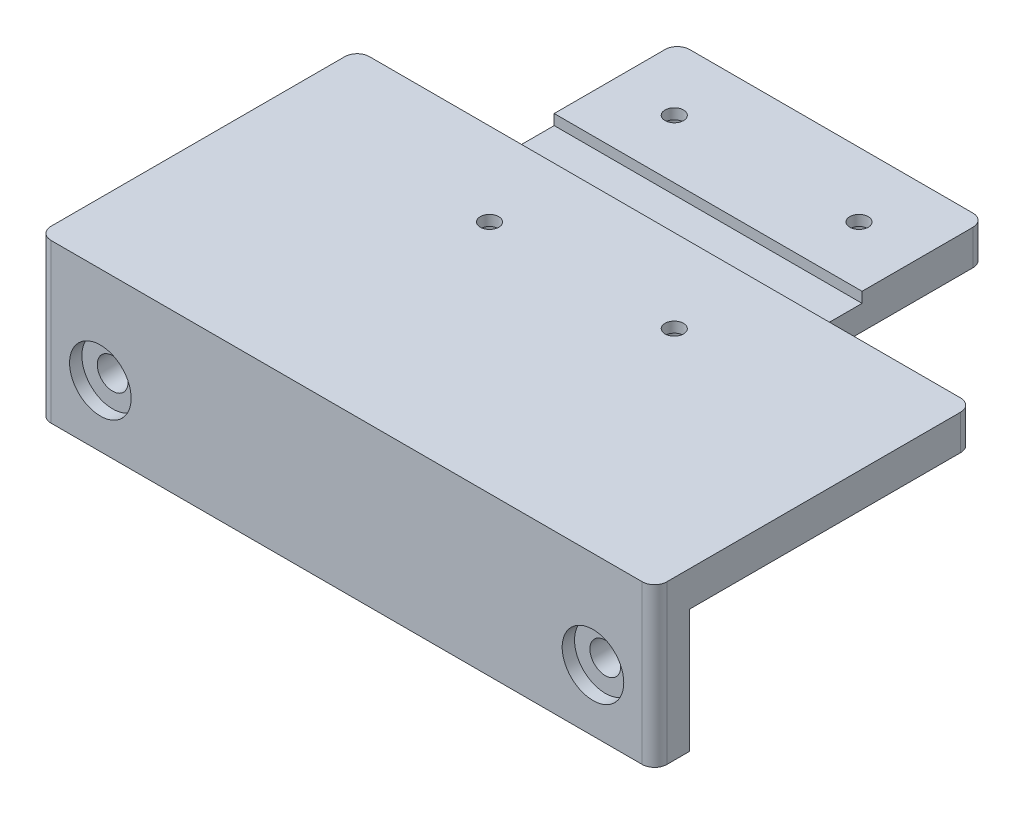
SolidWorks part; units mm, degrees
ref_plane "Front Plane" through (0, 0, 0) normal (0, 0, 1) x (1, 0, 0)
ref_plane "Top Plane" through (0, 0, 0) normal (0, 1, 0) x (1, 0, 0)
ref_plane "Right Plane" through (0, 0, 0) normal (1, 0, 0) x (0, 0, -1)
sketch "Sketch1" plane through (0, 0, 0) normal (1, 0, 0) x (0, 0, -1)
  line L0 (-20.5, 0) -> (-20.5, 5.5)
  line L1 (-20.5, 14.5) -> (-19.5, 14.5)
  line L2 (-19.5, 14.5) -> (-19.5, 5.5)
  line L3 (-19.5, 5.5) -> (-20.5, 5.5)
  line L4 (-20.5, 20) -> (-14.5, 20)
  line L5 (-20.5, 14.5) -> (-20.5, 20)
  line L6 (5.5, 20) -> (5.5, 19)
  line L7 (5.5, 19) -> (14.5, 19)
  line L8 (14.5, 19) -> (14.5, 20)
  line L9 (14.5, 20) -> (25.5, 20)
  line L10 (-5.5, 20) -> (-5.5, 19)
  line L11 (-5.5, 19) -> (-14.5, 19)
  line L12 (-14.5, 19) -> (-14.5, 20)
  line L13 (-5.5, 20) -> (5.5, 20)
  line L14 (-20.5, 0) -> (-26.2, 0)
  line L15 (-26.2, 0) -> (-26.2, 25.7)
  line L16 (-26.2, 25.7) -> (25.5, 25.7)
  line L17 (25.5, 25.7) -> (25.5, 20)
  line L19 (25.5, 24) -> (32.5, 24)
  line L20 (32.5, 24) -> (32.5, 25.7)
  line L21 (32.5, 25.7) -> (52.5, 25.7)
  line L22 (52.5, 25.7) -> (52.5, 20)
  line L23 (52.5, 20) -> (25.5, 20)
  point P8 (0, 20)
  point P22 (32.5, 28.1583)
  point P25 (25.1505, 20)
  point P28 (32.5, 23.1319)
  dimension "D1" = 20
  dimension "D2" = 9
  dimension "D3" = 1
  dimension "D4" = 46
  dimension "D5" = 11
  dimension "D6" = 5.7
  dimension "D7" = 11
  dimension "D8" = 7
  dimension "D9" = 20
  dimension "D10" = 4
extrude "Boss-Extrude1" add sketch "Sketch1" along normal mid plane 100 contours L17 L16 L15 L14 L0 L3 L2 L1 L5 L4 L12 L11 L10 L13 L6 L7 L8 L9 region at (0, 19.0839, 6.7595)
extrude "Boss-Extrude2" add sketch "Sketch1<3>" along normal mid plane 50 contours L23 L22 L21 L20 L19 L17 region at (0, 22.6824, -39.838)
sketch "Sketch1<3>" plane through (0, 0, 0) normal (1, 0, 0) x (0, 0, -1) same geometry as "Sketch1"
chamfer "Chamfer1" distance 1 12 edges at (0, 5.5, 19.5) (0, 14.5, 19.5) (0, 19, 14.5) (0, 19, 5.5) (0, 19, -5.5) (0, 19, -14.5) (-50, 10, 19.5) (50, 10, 19.5) (50, 19, 10) (-50, 19, 10) (50, 19, -10) (-50, 19, -10)
sketch "Sketch2" plane through (0, 20, 0) normal (0, -1, 0) x (1, 0, 0)
  line L0 (-25, -25.5) -> (-50, -25.5) construction
  line L2 (0, -52.5) -> (0, 26.2) construction
  line L3 (25, -52.5) -> (-25, -52.5) construction
  line L4 (50, 26.2) -> (-50, 26.2) construction
  line L5 (-25, -27) -> (25, -27) construction
  line L7 (-25, -52.5) -> (-25, -25.5) construction
  line L8 (25, -52.5) -> (25, -25.5) construction
  line L11 (-50, 5.5) -> (-50, -5.5) construction
  circle A0 centre (-15, -12) radius 1.5
  circle A1 centre (-15, -12) radius 2.5
  circle A2 centre (-15, -42) radius 2.5
  circle A3 centre (-15, -42) radius 1.5
  circle A4 centre (15, -42) radius 1.5
  circle A5 centre (15, -42) radius 2.5
  circle A6 centre (15, -12) radius 2.5
  circle A7 centre (15, -12) radius 1.5
  point P31 (-50, 0.4479)
  dimension "D1" = 2.5
  dimension "D2" = 1.5
  dimension "D3" = 13.5
  dimension "D4" = 35
  dimension "D5" = 15
extrude "Cut-Extrude1" cut sketch "Sketch2" against normal through all both and the other way through all contours A3 | A4 | A0 | A7 region at (-15, 20, -12) region at (-15, 20, -42) region at (15, 20, -42) region at (15, 20, -12)
extrude "Cut-Extrude2" cut sketch "Sketch2<3>" against normal blind 4 and the other way through all
sketch "Sketch2<3>" plane through (0, 20, 0) normal (0, -1, 0) x (1, 0, 0) same geometry as "Sketch2"
sketch "Sketch3" plane through (0, 0, 19.5) normal (0, 0, -1) x (-1, 0, 0)
  line L0 (-50, 13.5) -> (-50, 6.5) construction
  line L1 (0, 0) -> (0, 25.7) construction
  line L2 (-25, 25.7) -> (25, 25.7) construction
  circle A0 centre (-40, 10) radius 2.5
  circle A1 centre (-40, 10) radius 5
  circle A2 centre (40, 10) radius 5
  circle A3 centre (40, 10) radius 2.5
  point P7 (-50, 10)
  dimension "D1" = 2.5
  dimension "D2" = 5
  dimension "D3" = 10
extrude "Cut-Extrude3" cut sketch "Sketch3" against normal through all both and the other way through all contours A0 | A3 region at (40, 10, 19.5) region at (-40, 10, 19.5)
extrude "Cut-Extrude4" cut sketch "Sketch3<3>" along normal blind 2 from surface starting at face at (-42.5, 10, 26.2)
sketch "Sketch3<3>" plane through (0, 0, 19.5) normal (0, 0, -1) x (-1, 0, 0) same geometry as "Sketch3"
fillet "Fillet1" radius 2 6 edges at (-25, 22.85, -52.5) (25, 22.85, -52.5) (-50, 12.85, 26.2) (50, 12.85, 26.2) (-50, 22.85, -25.5) (50, 22.85, -25.5)
